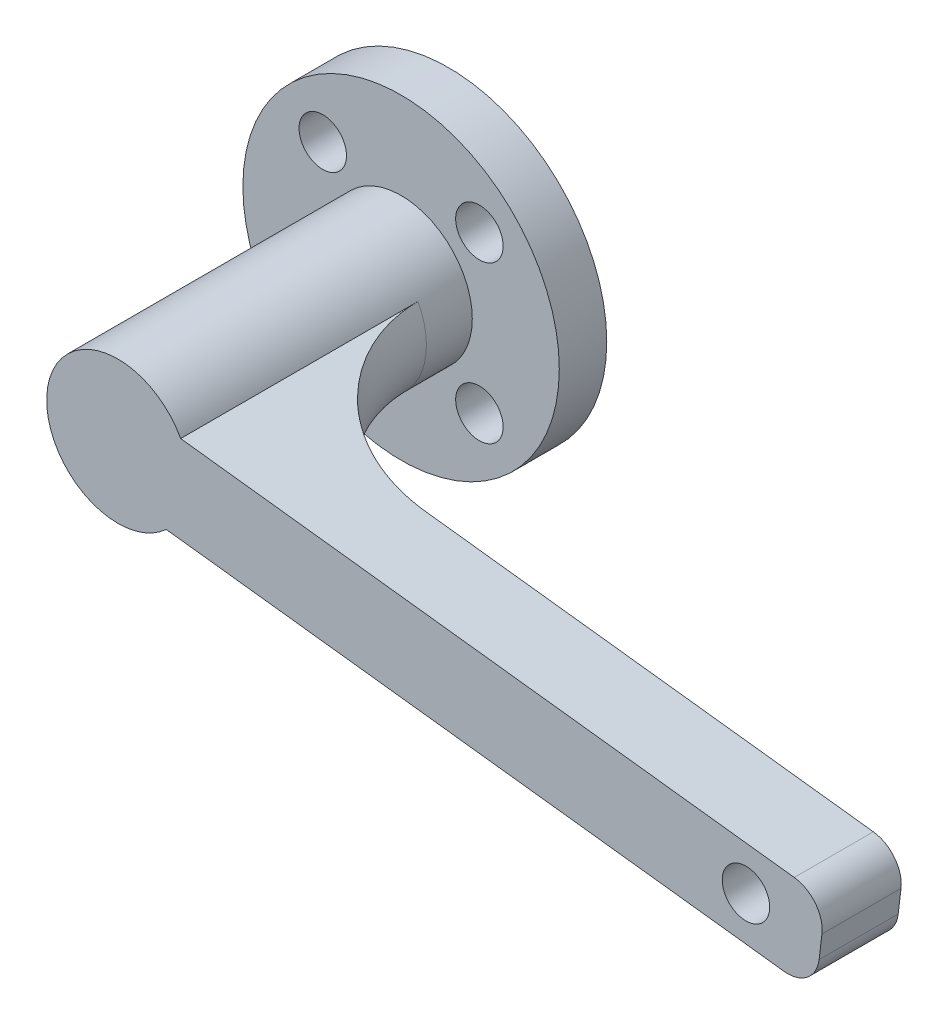
SolidWorks part; units mm, degrees
ref_plane "前视基准面" through (0, 0, 0) normal (0, 0, 1) x (1, 0, 0)
ref_plane "上视基准面" through (0, 0, 0) normal (0, 1, 0) x (1, 0, 0)
ref_plane "右视基准面" through (0, 0, 0) normal (1, 0, 0) x (0, 0, -1)
sketch "草图1" plane through (0, 0, 0) normal (0, 0, 1) x (1, 0, 0)
  circle A0 centre (0, 0) radius 10
  dimension "D1" = 20
extrude "凸台-拉伸1" add sketch "草图1" along normal blind 3
sketch "草图2" plane through (0, 0, 3) normal (0, 0, 1) x (1, 0, 0)
  line L1 (4.95, -4.95) -> (-4.95, -4.95)
  line L2 (4.95, -4.95) -> (4.95, 4.95)
  line L3 (4.95, 4.95) -> (-4.95, 4.95)
  line L4 (-4.95, -4.95) -> (-4.95, 4.95)
  line L5 (4.95, -4.95) -> (-4.95, 4.95) construction
  line L6 (4.95, 4.95) -> (-4.95, -4.95) construction
  circle A0 centre (0, 0) radius 1.5
  circle A2 centre (4.95, 4.95) radius 1.5
  circle A3 centre (-4.95, 4.95) radius 1.5
  circle A4 centre (-4.95, -4.95) radius 1.5
  circle A5 centre (4.95, -4.95) radius 1.5
  dimension "D1" = 3
  dimension "D2" = 9.9
  dimension "D4" = 3
  dimension "D3" = 9.9
extrude "切除-拉伸1" cut sketch "草图2" against normal through all contours L3 A3 L4 | L4 A3 L3 | L2 A2 L3 | L3 A2 L2 | L4 A4 L1 | L1 A4 L4 | L1 A5 L2 | L2 A5 L1 | A0 region at (-5.1622, -5.1622, 3) region at (-4.3134, -4.3134, 3) region at (4.3134, -4.3134, 3) region at (5.1622, -5.1622, 3) region at (-5.1622, 5.1622, 3) region at (-4.3134, 4.3134, 3) region at (4.3134, 4.3134, 3) region at (5.1622, 5.1622, 3)
sketch "草图3" plane through (0, 0, 3) normal (0, 0, 1) x (1, 0, 0)
  circle A0 centre (0, 0) radius 4.5
  circle A1 centre (-4.95, 4.95) radius 1.5 construction
  circle A2 centre (0, 0) radius 10
  circle A3 centre (0, 0) radius 10
  circle A4 centre (-4.95, 4.95) radius 1.5
  circle M5 centre (0, 0) radius 1.5
  dimension "D1" = 0
  dimension "D2" = 9
extrude "凸台-拉伸2" add sketch "草图3" along normal blind 12.9 contours A0 M5 region at (-4.3727, 0, 3)
sketch "草图4" plane through (0, 0, 0) normal (0, 0, -1) x (-1, 0, 0)
  circle A0 centre (0, 0) radius 1.5 construction
  circle A3 centre (0, 0) radius 1.5
extrude "凸台-拉伸4" add sketch "草图4" against normal up to surface (15.9 mm away) up to face at (1.5, 0, 15.9)
sketch "草图5" plane through (0, 0, 15.9) normal (0, 0, 1) x (1, 0, 0)
  line L0 (-0.2722, -0.1379) -> (44.4103, -5.4737) construction
  line L1 (44.7364, -2.7431) -> (44.0842, -8.2043)
  line L2 (44.0842, -8.2043) -> (-0.5983, -2.8685)
  line L3 (-0.5983, -2.8685) -> (0.0539, 2.5927)
  line L4 (44.7364, -2.7431) -> (0.0539, 2.5927)
  dimension "D1" = 45
  dimension "D2" = 2.75
extrude "凸台-拉伸5" add sketch "草图5" along normal blind 5
sketch "草图6" plane through (0, 0, 20.9) normal (0, 0, 1) x (1, 0, 0)
  line L0 (44.4103, -5.4737) -> (39.6974, -4.9109) construction
  line L1 (44.0842, -8.2043) -> (44.7364, -2.7431) construction
  line L2 (44.7364, -2.7431) -> (0.0539, 2.5927) construction
  circle A0 centre (39.6974, -4.9109) radius 1.5
  circle A1 centre (0, 0) radius 4.5 construction
  dimension "D1" = 3
  dimension "D2" = 40
extrude "切除-拉伸2" cut sketch "草图6" against normal through all
sketch "草图7" plane through (0, 0, 15.9) normal (0, 0, 1) x (1, 0, 0)
  line L3 (0.0539, 2.5927) -> (3.9664, 2.1255)
  line L4 (3.0544, -3.3047) -> (-0.5983, -2.8685)
  line L5 (-0.5983, -2.8685) -> (0.0539, 2.5927)
  line L6 (0.0539, 2.5927) -> (3.9664, 2.1255)
  line L7 (3.0544, -3.3047) -> (-0.5983, -2.8685)
  line L8 (-0.5983, -2.8685) -> (0.0539, 2.5927)
  arc A1 (3.9664, 2.1255) -> (3.0544, -3.3047) centre (0, 0) ccw
  arc A2 (3.9664, 2.1255) -> (3.0544, -3.3047) centre (0, 0) ccw
  dimension "D1" = 0
extrude "凸台-拉伸8" add sketch "草图7" along normal blind 5 contours L6 A2 L7 L8
fillet "圆角1" radius 10 1 edges at (4.4378, -0.7454, 15.9)
fillet "圆角2" radius 2 2 edges at (44.0842, -8.2043, 18.4) (44.7364, -2.7431, 18.4)
sketch "草图8" plane through (0, 0, 0) normal (0, 0, -1) x (-1, 0, 0)
  circle A0 centre (0, 0) radius 3.75
  dimension "D1" = 7.5
extrude "切除-拉伸3" cut sketch "草图8" against normal blind 3
